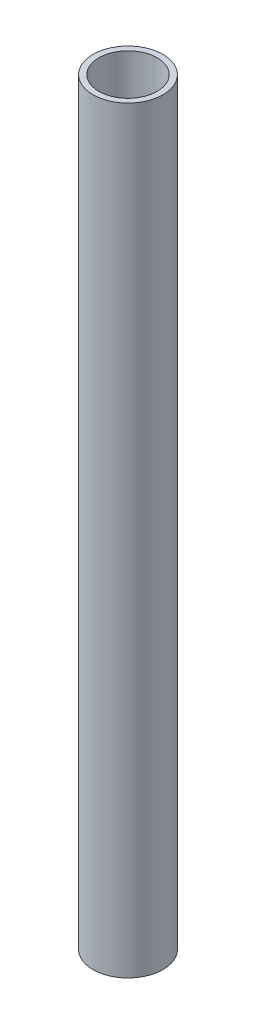
SolidWorks part; units mm, degrees
ref_plane "Front Plane" through (0, 0, 0) normal (0, 0, 1) x (1, 0, 0)
ref_plane "Top Plane" through (0, 0, 0) normal (0, 1, 0) x (1, 0, 0)
ref_plane "Right Plane" through (0, 0, 0) normal (1, 0, 0) x (0, 0, -1)
sketch "Sketch1" plane through (0, 0, 0) normal (0, 1, 0) x (1, 0, 0)
  circle A0 centre (0, 0) radius 7.62
  circle A1 centre (0, 0) radius 6.35
  dimension "D1" = 12.7
  dimension "D2" = 15.24
extrude "Boss-Extrude1" add sketch "Sketch1" along normal blind 165.1
ref_plane "Plane1" through (-7.62, 0, 0) normal (-1, 0, 0) x (0, 0, 1)
sketch "Sketch2" plane through (-7.62, 0, 0) normal (-1, 0, 0) x (0, 0, 1)
  line L0 (0, 165.1) -> (0, 0) construction
  line L1 (7.62, 165.1) -> (-7.62, 165.1) construction
  line L2 (0, 154.0589) -> (-7.62, 154.0589) construction
  line L3 (-7.62, 165.1) -> (-7.62, 0) construction
  line L6 (0, 154.0589) -> (7.62, 154.0589) construction
  line L7 (7.62, 0) -> (7.62, 165.1) construction
  line L9 (-3.81, 154.0589) -> (-3.81, 131.7175) construction
  line L12 (3.81, 154.0589) -> (3.81, 131.7175) construction
  line L13 (3.81, 131.7175) -> (-3.81, 131.7175) construction
  line L14 (-3.81, 154.0589) -> (-3.81, 131.7175) construction
  line L15 (-2.286, 154.0589) -> (-2.286, 131.7175)
  line L16 (-5.334, 154.0589) -> (-5.334, 131.7175)
  line L17 (3.81, 131.7175) -> (3.81, 138.0869) construction
  line L18 (2.286, 131.7175) -> (2.286, 138.0869)
  line L19 (5.334, 131.7175) -> (5.334, 138.0869)
  line L20 (-3.81, 131.7175) -> (3.81, 131.7175) construction
  line L21 (-3.81, 133.2415) -> (3.81, 133.2415)
  line L22 (-3.81, 130.1935) -> (3.81, 130.1935)
  arc A0 (-2.286, 154.0589) -> (-5.334, 154.0589) centre (-3.81, 154.0589) ccw
  arc A1 (-5.334, 131.7175) -> (-2.286, 131.7175) centre (-3.81, 131.7175) ccw
  arc A2 (2.286, 131.7175) -> (5.334, 131.7175) centre (3.81, 131.7175) ccw
  arc A3 (5.334, 138.0869) -> (2.286, 138.0869) centre (3.81, 138.0869) ccw
  arc A4 (-3.81, 133.2415) -> (-3.81, 130.1935) centre (-3.81, 131.7175) ccw
  arc A5 (3.81, 130.1935) -> (3.81, 133.2415) centre (3.81, 131.7175) ccw
  point P15 (-3.81, 142.8882)
  point P20 (3.81, 134.9022)
  point P29 (0, 131.7175)
  dimension "D1" = 1.524
  dimension "D2" = 1.524
  dimension "D3" = 1.524
extrude "Cut-Extrude1" cut sketch "Sketch2" against normal up to surface (2.54 mm away) contours A1 | A1 | A1 | L16 A1 L15 A0 | L19 A3 L18 A2 region at (-7.62, 131.6385, 0) region at (-7.62, 131.7932, -3.7343) up to face at (0, 165.1, 6.35)
fillet "Fillet3" radius 2.54 2 edges at (-6.5966, 133.2415, 2.286) (-6.5966, 133.2415, -2.286)
